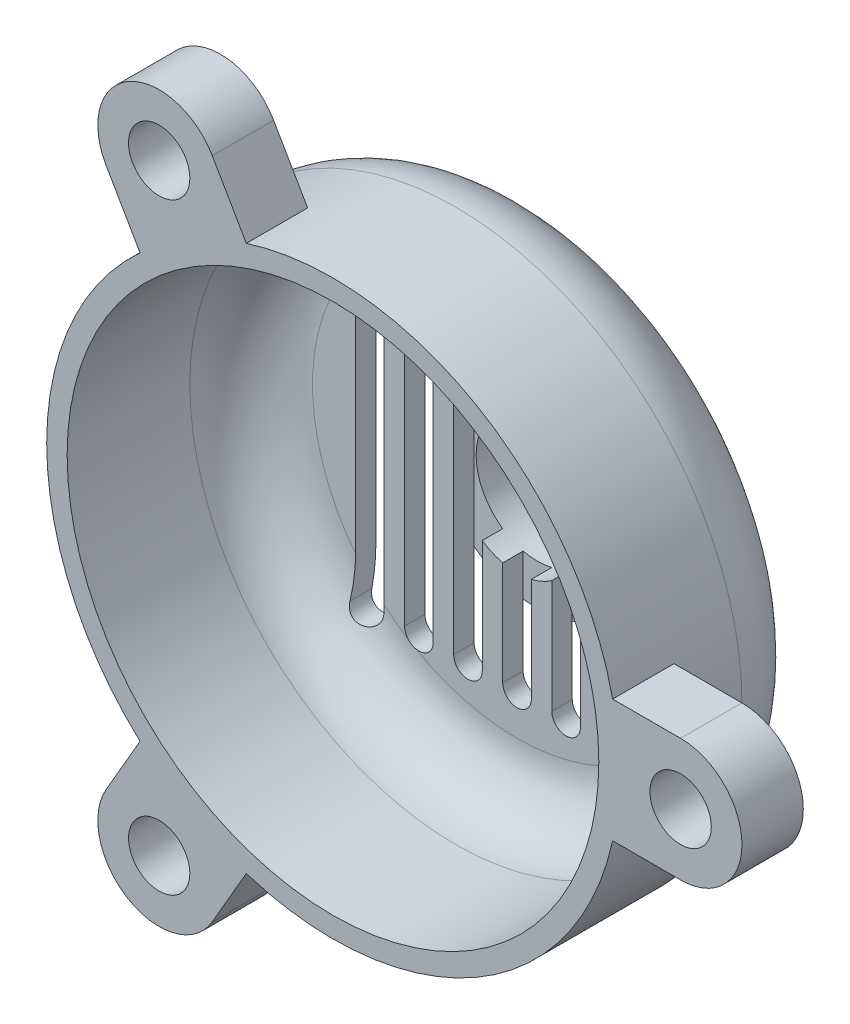
SolidWorks part; units mm, degrees
ref_plane "Front Plane" through (0, 0, 0) normal (0, 0, 1) x (1, 0, 0)
ref_plane "Top Plane" through (0, 0, 0) normal (0, 1, 0) x (1, 0, 0)
ref_plane "Right Plane" through (0, 0, 0) normal (1, 0, 0) x (0, 0, -1)
sketch "Sketch1" plane through (0, 0, 0) normal (0, 0, 1) x (1, 0, 0)
  circle A0 centre (0, 0) radius 3.5
  dimension "D1" = 7
extrude "Boss-Extrude1" add sketch "Sketch1" along normal mid plane 2.5
fillet "Fillet1" radius 1 1 edges at (3.5, 0, -1.25)
shell "Shell1" thickness 0.25 removed face at (3.5, 0, 1.25)
sketch "Sketch2" plane through (0, 0, -1.25) normal (0, 0, -1) x (-1, 0, 0)
  line L0 (0, 2) -> (0, -2) construction
  line L1 (0.175, 2) -> (0.175, -2)
  line L2 (-0.175, 2) -> (-0.175, -2)
  line L3 (-4.9403, 0) -> (5.2411, 0) construction
  arc A0 (0.175, 2) -> (-0.175, 2) centre (0, 2) ccw
  arc A1 (-0.175, -2) -> (0.175, -2) centre (0, -2) ccw
  point P3 (0, 0)
  dimension "D1" = 4
  dimension "D2" = 0.35
extrude "Cut-Extrude1" cut sketch "Sketch2" against normal through all
pattern_linear "LPattern1" count 4 spacing 0.6 along (1, 0, 0) of "Cut-Extrude1"
pattern_linear "LPattern2" count 4 spacing 0.6 along (-1, 0, 0) of "Cut-Extrude1"
sketch "Sketch3" plane through (0, 0, -1.25) normal (0, 0, -1) x (-1, 0, 0)
  circle A0 centre (0, 0) radius 1.25
  circle A1 centre (0, 0) radius 0.75
  dimension "D1" = 1.5
  dimension "D2" = 2.5
extrude "Boss-Extrude2" add sketch "Sketch3" along normal blind 0.75 contours A0
extrude "Cut-Extrude2" cut sketch "Sketch3<3>" against normal through all both and the other way through all contours A1
sketch "Sketch3<3>" plane through (0, 0, -1.25) normal (0, 0, -1) x (-1, 0, 0) same geometry as "Sketch3"
sketch "Sketch4" plane through (0, 0, 1.25) normal (0, 0, 1) x (1, 0, 0)
  line L0 (4.25, 0.75) -> (3.4187, 0.75)
  line L1 (4.25, -0.75) -> (3.4187, -0.75)
  arc A0 (4.25, -0.75) -> (4.25, 0.75) centre (4.25, 0) ccw
  circle A1 centre (4.25, 0) radius 0.375
  circle A2 centre (0, 0) radius 3.5 construction
  arc A3 (3.4187, -0.75) -> (3.4187, 0.75) centre (0, 0) ccw
  dimension "D1" = 0.75
  dimension "D2" = 1.5
  dimension "D3" = 4.25
extrude "Boss-Extrude3" add sketch "Sketch4" against normal blind 0.75
pattern_circular "CirPattern1" count 3 over 360 about axis through (0, 0, 1.25) along (0, 0, 1) of "Boss-Extrude3"
